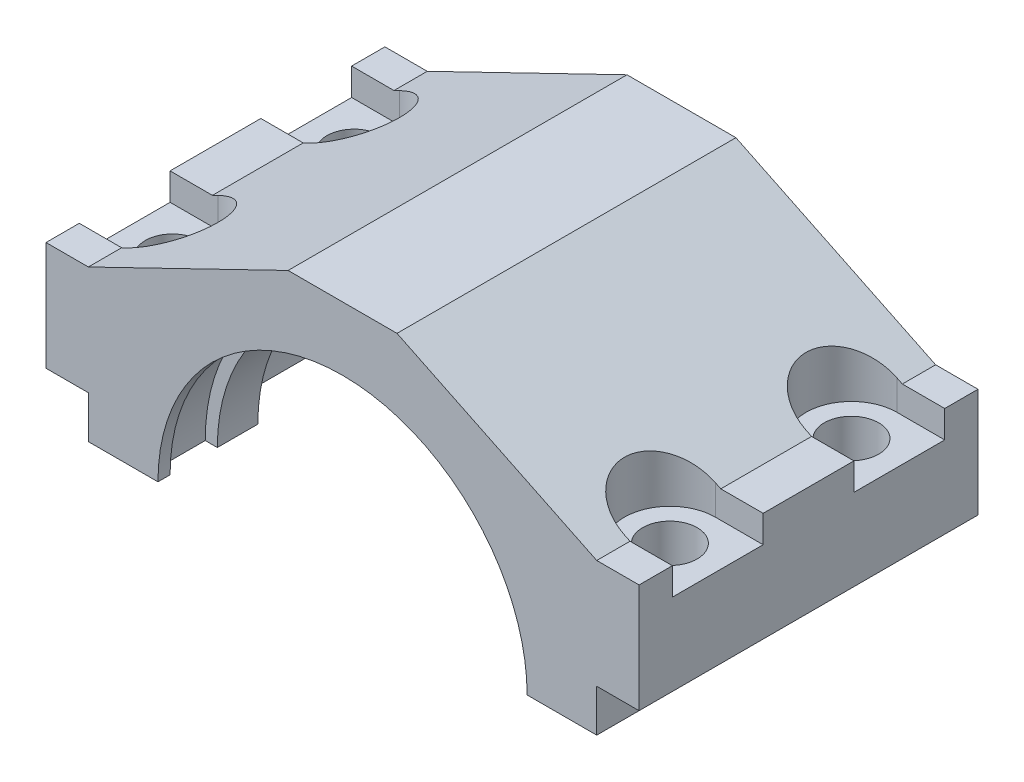
SolidWorks part; units mm, degrees
ref_plane "Ön Düzlem" through (0, 0, 0) normal (0, 0, 1) x (1, 0, 0)
ref_plane "Üst Düzlem" through (0, 0, 0) normal (0, 1, 0) x (1, 0, 0)
ref_plane "Sağ Düzlem" through (0, 0, 0) normal (1, 0, 0) x (0, 0, -1)
sketch "Çizim1" plane through (0, 0, 0) normal (0, 0, 1) x (1, 0, 0)
  line L0 (9, 0) -> (-9, 0)
  line L1 (-9, 0) -> (-42, -16)
  line L2 (-42, -16) -> (-49, -16)
  line L3 (-49, -16) -> (-49, -34)
  line L4 (-49, -34) -> (-42, -34)
  line L5 (-42, -34) -> (-42, -41)
  line L6 (-42, -41) -> (-30.5, -41)
  line L7 (0, 0) -> (0, -72.3158) construction
  line L8 (42, -16) -> (49, -16)
  line L9 (49, -16) -> (49, -34)
  line L10 (49, -34) -> (42, -34)
  line L11 (42, -34) -> (42, -41)
  line L12 (42, -41) -> (30.5, -41)
  line L13 (9, 0) -> (42, -16)
  arc A0 (-30.5, -41) -> (30.5, -41) centre (0, -41) cw
  point P4 (0, 0)
  dimension "D8" = 30.5
  dimension "D1" = 18
  dimension "D2" = 18
  dimension "D3" = 7
  dimension "D4" = 41
  dimension "D5" = 7
  dimension "D6" = 49
  dimension "D7" = 11.5
extrude "Yükseklik-Ekstrüzyon1" add sketch "Çizim1" along normal mid plane 56
ref_plane "Düzlem1" through (0, 0, 28) normal (0, 0, 1) x (1, 0, 0)
ref_plane "Düzlem2" through (0, 0, 26) normal (0, 0, 1) x (1, 0, 0)
sketch "Çizim2" plane through (0, 0, 26) normal (0, 0, 1) x (1, 0, 0)
  line L0 (-32.5, -41) -> (32.5, -41)
  arc A0 (32.5, -41) -> (-32.5, -41) centre (0, -41) ccw
  dimension "D1" = 65
extrude "Kes-Ekstrüzyon1" cut sketch "Çizim2" against normal blind 7.81
ref_plane "Düzlem3" through (0, 0, 11.5) normal (0, 0, 1) x (1, 0, 0)
sketch "Çizim3" plane through (0, 0, 11.5) normal (0, 0, 1) x (1, 0, 0)
  line L0 (-36, -41) -> (36, -41)
  arc A0 (36, -41) -> (-36, -41) centre (0, -41) ccw
  dimension "D1" = 72
extrude "Kes-Ekstrüzyon2" cut sketch "Çizim3" against normal blind 23
ref_plane "Düzlem4" through (0, 0, -17) normal (0, 0, 1) x (1, 0, 0)
sketch "Çizim4" plane through (0, 0, -17) normal (0, 0, 1) x (1, 0, 0)
  line L0 (-32.5, -41) -> (32.5, -41)
  arc A0 (32.5, -41) -> (-32.5, -41) centre (0, -41) ccw
  dimension "D1" = 65
extrude "Kes-Ekstrüzyon3" cut sketch "Çizim4" against normal blind 9
ref_plane "Düzlem7" through (0, -16, 0) normal (0, 1, 0) x (1, 0, 0)
sketch "Çizim5" plane through (0, -16, 0) normal (0, 1, 0) x (1, 0, 0)
  line L0 (49, -28) -> (41.09, -28) construction
  line L1 (42, -28) -> (9, -28) construction
  line L2 (41.09, -28) -> (41.09, -15) construction
  line L3 (41.09, -15) -> (41.09, -7.5) construction
  line L4 (41.09, -7.5) -> (41.09, 28) construction
  line L5 (42, 28) -> (9, 28) construction
  line L6 (41.09, -7.5) -> (49, -7.5)
  line L7 (49, -28) -> (49, 28) construction
  line L8 (41.09, -22.5) -> (49, -22.5)
  line L9 (49, 0) -> (26.5054, 0) construction
  line L10 (41.09, 22.5) -> (49, 22.5)
  line L11 (41.09, 7.5) -> (49, 7.5)
  line L12 (49, 22.5) -> (49, 7.5)
  line L13 (49, -7.5) -> (49, -22.5)
  arc A0 (41.09, -7.5) -> (41.09, -22.5) centre (41.09, -15) ccw
  arc A1 (41.09, 7.5) -> (41.09, 22.5) centre (41.09, 15) cw
  dimension "D3" = 15
  dimension "D1" = 7.91
  dimension "D2" = 13
extrude "Kes-Ekstrüzyon4" cut sketch "Çizim5" along normal blind 9
extrude "Kes-Ekstrüzyon5" cut sketch "Çizim5<2>" against normal blind 4.5
sketch "Çizim5<2>" plane through (0, -16, 0) normal (0, 1, 0) x (1, 0, 0) same geometry as "Çizim5"
mirror "Aynalama1" about plane through (0, 0, 0) normal (1, 0, 0) of "Kes-Ekstrüzyon5", "Kes-Ekstrüzyon4"
sketch "Çizim7" plane through (0, -20.5, 0) normal (0, 1, 0) x (1, 0, 0)
  circle A0 centre (-41.09, -15) radius 4.5
  circle A1 centre (-41.09, 15) radius 4.5
  dimension "D1" = 9
  dimension "D2" = 9
extrude "Kes-Ekstrüzyon6" cut sketch "Çizim7" against normal through all
mirror "Aynalama2" about plane through (0, 0, 0) normal (1, 0, 0) of "Kes-Ekstrüzyon6"
